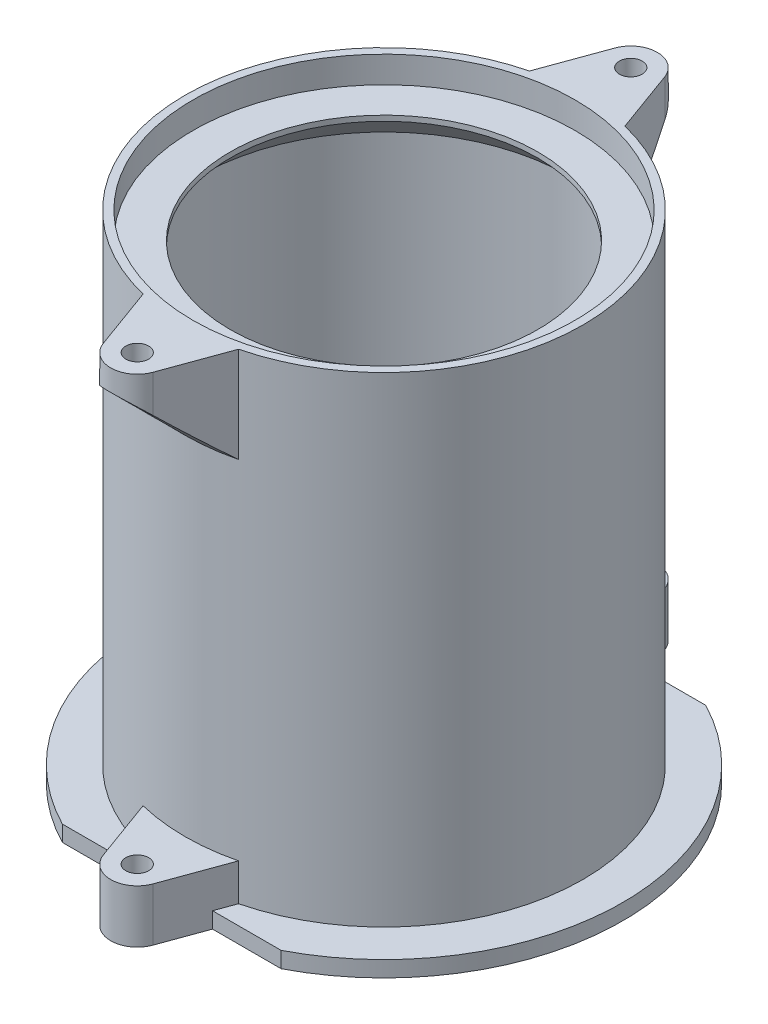
SolidWorks part; units mm, degrees
ref_plane "前视基准面" through (0, 0, 0) normal (0, 0, 1) x (1, 0, 0)
ref_plane "上视基准面" through (0, 0, 0) normal (0, 1, 0) x (1, 0, 0)
ref_plane "右视基准面" through (0, 0, 0) normal (1, 0, 0) x (0, 0, -1)
sketch "草图1" plane through (0, 0, 0) normal (0, 1, 0) x (1, 0, 0)
  circle A0 centre (0, 0) radius 29
  circle A1 centre (0, 0) radius 37.5
  dimension "D1" = 58
  dimension "D2" = 75
extrude "凸台-拉伸1" add sketch "草图1" along normal blind 4
sketch "草图2" plane through (0, 4, 0) normal (0, 1, 0) x (1, 0, 0)
  circle A0 centre (0, 0) radius 36
  circle A1 centre (0, 0) radius 37.5 construction
  circle A2 centre (0, 0) radius 37.5
  dimension "D1" = 72
extrude "凸台-拉伸2" add sketch "草图2" along normal blind 5
sketch "草图3" plane through (0, 0, 0) normal (0, -1, 0) x (1, 0, 0)
  circle A0 centre (0, 0) radius 37.5 construction
  circle A1 centre (0, 0) radius 29 construction
  circle A2 centre (0, 0) radius 37.5
  circle A3 centre (0, 0) radius 29
extrude "凸台-拉伸3" add sketch "草图3" along normal blind 84.5
sketch "草图4" plane through (0, -84.5, 0) normal (0, -1, 0) x (1, 0, 0)
  line L0 (-50, 40) -> (50, -40) construction
  line L1 (-50, 40) -> (50, 40)
  line L2 (-50, 40) -> (-50, -40)
  line L3 (-50, -40) -> (50, -40)
  line L4 (50, 40) -> (50, -40)
  circle A0 centre (0, 0) radius 37.5 construction
  circle A1 centre (0, 0) radius 37.5
  dimension "D1" = 100
  dimension "D2" = 80
extrude "凸台-拉伸4" add sketch "草图4" against normal blind 3
sketch "草图5" plane through (0, -84.5, 0) normal (0, -1, 0) x (1, 0, 0)
  line L0 (0, 46.5) -> (0, -46.5) construction
  circle A0 centre (0, 46.5) radius 2.15
  circle A1 centre (0, -46.5) radius 2.15
  circle A2 centre (0, 46.5) radius 5
  circle A3 centre (0, -46.5) radius 5
  dimension "D1" = 4.3
  dimension "D3" = 10
  dimension "D2" = 93
extrude "凸台-拉伸5" add sketch "草图5" against normal up to surface (93.5 mm away) separate body up to face at (0, 9, 37.5)
sketch "草图6" plane through (0, -81.5, 0) normal (0, 1, 0) x (1, 0, 0)
  line L0 (-4.6985, 48.2101) -> (-8.9951, 36.4052)
  line L1 (0, 46.5) -> (0, -46.5) construction
  line L2 (4.6985, 48.2101) -> (8.9951, 36.4052)
  line L3 (-37.5, 0) -> (37.5, 0) construction
  line L4 (4.6985, -48.2101) -> (8.9951, -36.4052)
  line L5 (-4.6985, -48.2101) -> (-8.9951, -36.4052)
  circle A0 centre (0, 46.5) radius 5 construction
  circle A1 centre (0, 0) radius 37.5 construction
  arc A2 (-4.6985, 48.2101) -> (4.6985, 48.2101) centre (0, 46.5) ccw
  arc A3 (8.9951, 36.4052) -> (-8.9951, 36.4052) centre (0, 0) ccw
  circle A4 centre (0, 0) radius 37.5 construction
  arc A5 (8.9951, -36.4052) -> (-8.9951, -36.4052) centre (0, 0) cw
  arc A6 (-4.6985, -48.2101) -> (4.6985, -48.2101) centre (0, -46.5) cw
  dimension "D1" = 20
extrude "凸台-拉伸6" add sketch "草图6" along normal up to surface and the other way up to surface up to face at (0, 9, 37.5) other way up to face at (0, -84.5, -29)
combine bodies "组合2" operation type add bodies to combine 105 106 107
sketch "草图7" plane through (0, -81.5, 0) normal (0, 1, 0) x (1, 0, 0)
  circle A0 centre (0, 0) radius 40
  circle A1 centre (0, 0) radius 36 construction
  circle A2 centre (0, 0) radius 36 construction
  circle A3 centre (0, 0) radius 36
  dimension "D1" = 4
sketch "草图8" plane through (0, -84.5, 0) normal (0, -1, 0) x (1, 0, 0)
  circle A0 centre (0, 0) radius 35
  dimension "D1" = 70
extrude "切除-拉伸1" cut sketch "草图8" against normal offset from surface (87.5 mm away) 1 up to face at (0, 4, 29)
chamfer "倒角1" distance 6 angle 45 1 edges at (0, 3, 35)
sketch "草图9" plane through (0, 0, 0) normal (0, 0, 1) x (1, 0, 0)
  line L0 (-37.5, -9) -> (-60, 13.5)
  line L1 (-37.5, 9) -> (-37.5, -81.5) construction
  line L2 (-60, 13.5) -> (-60, -74.5)
  line L3 (-60, -74.5) -> (-37.5, -74.5)
  line L4 (36, 9) -> (-36, 9) construction
  line L5 (-7.6867, -84.5) -> (-50, -84.5) construction
  line L6 (-37.5, -9) -> (-37.5, -74.5)
  point P7 (-38.027, -74.5)
  dimension "D1" = 60
  dimension "D2" = 45
  dimension "D3" = 18
  dimension "D4" = 10
ref_axis "基准轴1" through (0, 9, 0) along (0, -1, 0)
revolve "切除-旋转1" cut sketch "草图9" angle 360 about axis through (0, 9, 0) along (0, -1, 0)
sketch "草图11" plane through (0, -81.5, 0) normal (0, 1, 0) x (1, 0, 0)
  line L0 (-20.6155, 40) -> (-50, 40)
  line L1 (-50, 40) -> (-7.6867, 40) construction
  line L2 (-50, 40) -> (-50, -40)
  line L3 (-50, -40) -> (-20.6155, -40)
  line L4 (-7.6867, -40) -> (-50, -40) construction
  line L5 (20.6155, 40) -> (50, 40)
  line L6 (7.6867, 40) -> (50, 40) construction
  line L7 (50, 40) -> (50, -40)
  line L8 (50, -40) -> (20.6155, -40)
  line L9 (50, -40) -> (7.6867, -40) construction
  arc A0 (20.6155, -40) -> (20.6155, 40) centre (0, 0) ccw
  arc A1 (-20.6155, 40) -> (-20.6155, -40) centre (0, 0) ccw
  dimension "D1" = 90
extrude "切除-拉伸2" cut sketch "草图11" against normal through all
